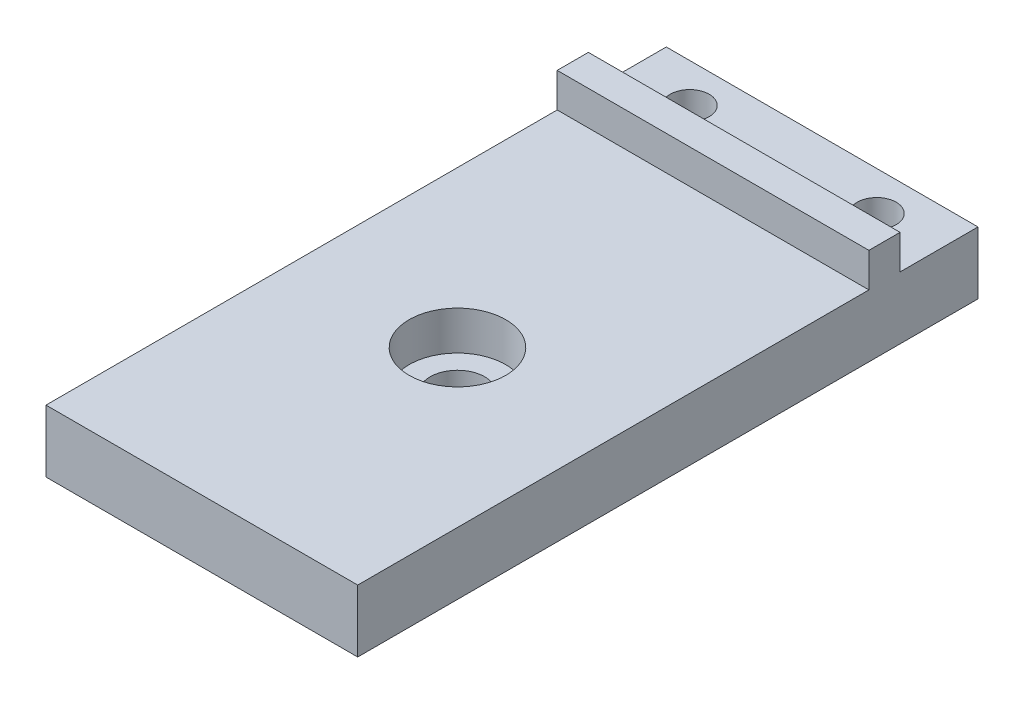
SolidWorks part; units mm, degrees
note: The reader was unsure of these and kept them because the rebuilt part matched: shared geometry of "草图4<3>", "草图5<6>", "草图6<3>", "草图1<3>", "草图7<4>".
ref_plane "前视基准面" through (0, 0, 0) normal (0, 0, 1) x (1, 0, 0)
ref_plane "上视基准面" through (0, 0, 0) normal (0, 1, 0) x (1, 0, 0)
ref_plane "右视基准面" through (0, 0, 0) normal (1, 0, 0) x (0, 0, -1)
other "Configuration Table"
sketch "草图1" plane through (0, 0, 0) normal (0, 1, 0) x (1, 0, 0)
  line L1 (0, 0) -> (20, 0)
  line L2 (0, 0) -> (0, -32.8)
  line L3 (0, -32.8) -> (20, -32.8)
  line L4 (20, 0) -> (20, -32.8)
  dimension "D1" = 32.8
  dimension "D2" = 20
extrude "凸台-拉伸1" add sketch "草图1" along normal blind 4
sketch "草图3" plane through (0, 4, 0) normal (0, 1, 0) x (-1, 0, 0)
  line L0 (-7.904, 2.2197) -> (-7.2, 13.5434)
  line L1 (-12.096, 2.2197) -> (-12.8, 13.5434)
  line L2 (-10, 2.35) -> (-10, 30.45) construction
  line L3 (-20, 0) -> (-20, 32.8) construction
  line L4 (0, 0) -> (-20, 0) construction
  line L5 (-12.8, 19.2566) -> (-12.096, 30.5803)
  line L6 (-7.904, 30.5803) -> (-7.2, 19.2566)
  line L7 (-12.8, 13.5434) -> (-7.2, 13.5434) construction
  line L8 (-12.8, 19.2566) -> (-7.2, 19.2566) construction
  circle A0 centre (-10, 16.4) radius 4
  circle A1 centre (-10, 2.35) radius 2.1
  circle A2 centre (-10, 30.45) radius 2.1
  point P13 (-20, 16.4)
  point P18 (-10, 0)
  dimension "D1" = 4.2
  dimension "D2" = 14.05
  dimension "D4" = 5.6
extrude "切除-拉伸1" cut sketch "草图3" against normal blind 1.6 contours A1 L0 A0 L1 | A2 L5 A0 L6
sketch "草图4" plane through (0, 0, 0) normal (0, -1, 0) x (1, 0, 0)
  line L0 (20, 0) -> (20, 32.8) construction
  line L2 (0, 32.8) -> (20, 32.8) construction
  line L3 (0, 0) -> (0, 32.8) construction
  line L4 (0, 0) -> (20, 0) construction
  circle A0 centre (4, 4) radius 1.25
  circle A1 centre (4, 28.8) radius 1.25
  circle A2 centre (16, 4) radius 1.25
  circle A3 centre (16, 28.8) radius 1.25
  circle A5 centre (4, 4) radius 2
  circle A6 centre (4, 28.8) radius 2
  circle A7 centre (16, 28.8) radius 2
  circle A8 centre (16, 4) radius 2
  dimension "D1" = 2.5
  dimension "D2" = 4
  dimension "D3" = 4
  dimension "D4" = 4
  dimension "D5" = 4
  dimension "D6" = 4
extrude "切除-拉伸2" cut sketch "草图4" against normal blind 1.5 contours A6 | A7 | A5 | A8
extrude "切除-拉伸3" cut sketch "草图4<3>" against normal through all contours A1 | A3 | A2 | A0
sketch "草图4<3>" plane through (0, 0, 0) normal (0, -1, 0) x (1, 0, 0) same geometry as "草图4"
sketch "草图5" plane through (0, 0, 0) normal (0, 0, -1) x (-1, 0, 0)
  line L0 (-20, 4) -> (0, 4)
  line L1 (-20, 6.2) -> (0, 6.2)
  line L2 (-20, 6.2) -> (-20, 0)
  line L3 (-20, 0) -> (0, 0)
  line L4 (0, 6.2) -> (0, 0)
  dimension "D1" = 6.2
  dimension "D2" = 20
extrude "凸台-拉伸4" add sketch "草图5" along normal blind 2 contours L4 L3 L2 L1
extrude "凸台-拉伸5" add sketch "草图5<6>" along normal blind 5 from surface at 2 starting at face at (10, 3.1, -2)
sketch "草图5<6>" plane through (0, 0, 0) normal (0, 0, -1) x (-1, 0, 0) same geometry as "草图5"
sketch "草图6" plane through (0, 0, 0) normal (0, -1, 0) x (1, 0, 0)
  line L0 (20, -7) -> (0, -7) construction
  line L1 (0, -7) -> (0, 32.8) construction
  line L2 (20, -7) -> (20, 32.8) construction
  circle A0 centre (4, -4.5) radius 1.25
  circle A1 centre (4, -4.5) radius 2
  circle A2 centre (16, -4.5) radius 1.25
  circle A3 centre (16, -4.5) radius 2
  dimension "D4" = 2.5
  dimension "D5" = 4
  dimension "D1" = 2.5
  dimension "D2" = 4
  dimension "D3" = 4
extrude "切除-拉伸4" cut sketch "草图6" against normal through all contours A0 | A2
extrude "切除-拉伸5" cut sketch "草图6<3>" against normal blind 1.5 contours A1 | A3
sketch "草图6<3>" plane through (0, 0, 0) normal (0, -1, 0) x (1, 0, 0) same geometry as "草图6"
extrude "凸台-拉伸6" add sketch "草图1<3>" along normal up to surface (4 mm away) up to face at (4, 4, 2.75)
sketch "草图1<3>" plane through (0, 0, 0) normal (0, 1, 0) x (1, 0, 0) same geometry as "草图1"
sketch "草图7" plane through (0, 4, 0) normal (0, 1, 0) x (1, 0, 0)
  circle A0 centre (10, -16.4) radius 3.1
  circle A2 centre (10, -16.4) radius 1.75
  dimension "D1" = 6.2
  dimension "D2" = 3.5
extrude "切除-拉伸7" cut sketch "草图7" against normal blind 2.5 contours A0
extrude "切除-拉伸8" cut sketch "草图7<4>" against normal through all contours A2
sketch "草图7<4>" plane through (0, 4, 0) normal (0, 1, 0) x (1, 0, 0) same geometry as "草图7"
